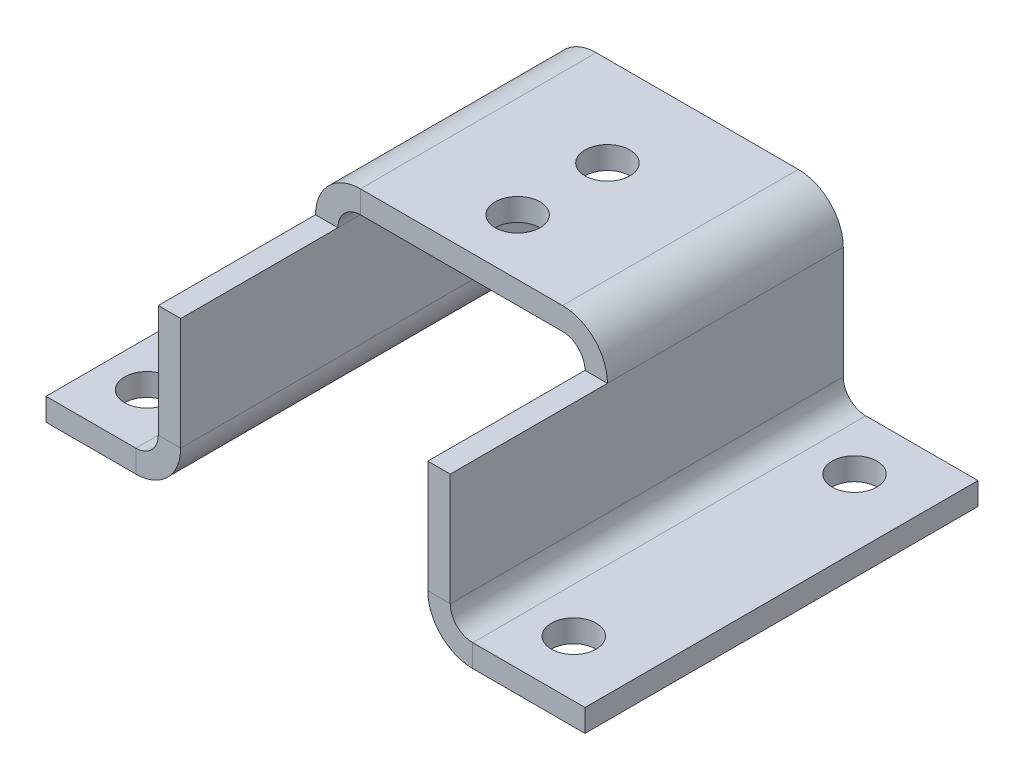
SolidWorks part; units mm, degrees
note: The reader was unsure of these and kept them because the rebuilt part matched: flange length of "Edge-Flange1", "Edge-Flange2", "Edge-Flange3", "Edge-Flange4".
ref_plane "Front Plane" through (0, 0, 0) normal (0, 0, 1) x (1, 0, 0)
ref_plane "Top Plane" through (0, 0, 0) normal (0, 1, 0) x (1, 0, 0)
ref_plane "Right Plane" through (0, 0, 0) normal (1, 0, 0) x (0, 0, -1)
sketch "Sketch1" plane through (0, 0, 0) normal (0, 1, 0) x (1, 0, 0)
  line L1 (6, -17.5) -> (-6, -17.5)
  line L2 (6, -17.5) -> (6, 17.5)
  line L3 (6, 17.5) -> (-6, 17.5)
  line L4 (-6, -17.5) -> (-6, 17.5)
  line L5 (6, -17.5) -> (-6, 17.5) construction
  line L6 (6, 17.5) -> (-6, -17.5) construction
  point P0 (0, 0)
  dimension "D1" = 12
  dimension "D2" = 35
base flange "Base-Flange1" sketch "Sketch1" thickness 2 reverse thickness direction no parameters "D1"=2
edge flange "Edge-Flange1" sketch "Sketch8" flange angle 90 flange length 16 flange position material inside bend radius 2 thickness 2 relief rectangular parameters "D6"=10
sketch "Sketch8" plane through (6, 0, 0) normal (1, 0, 0) x (0, 0, -1)
  line L0 (-17.5, 0) -> (17.5, 0) construction
  line L1 (-17.5, 0) -> (17.5, 0)
  line L2 (-17.5, 0) -> (-17.5, 16)
  line L3 (-17.5, 16) -> (17.5, 16)
  line L4 (17.5, 16) -> (17.5, 0)
bend "EdgeBend1" bend radius 2 bend angle 90 parameters "D5"=1
edge flange "Edge-Flange2" sketch "Sketch11" flange angle 90 flange length 24 flange position material inside bend radius 2 thickness 2 relief rectangular parameters "D6"=10
sketch "Sketch11" plane through (6, 16, 0) normal (0, 1, 0) x (0, 0, 1)
  line L0 (-17.5, 0) -> (17.5, 0) construction
  line L1 (-17.5, 0) -> (17.5, 0)
  line L2 (-17.5, 0) -> (-17.5, 24)
  line L3 (-17.5, 24) -> (17.5, 24)
  line L4 (17.5, 24) -> (17.5, 0)
bend "EdgeBend2" bend radius 2 bend angle 90 parameters "D5"=2
edge flange "Edge-Flange3" sketch "Sketch14" flange angle 90 flange length 16 flange position material inside bend radius 2 thickness 2 relief rectangular parameters "D6"=10
sketch "Sketch14" plane through (30, 14, 0) normal (1, 0, 0) x (0, 0, 1)
  line L0 (17.5, 0) -> (-17.5, 0) construction
  line L1 (17.5, 0) -> (-17.5, 0)
  line L2 (-17.5, 0) -> (-17.5, 16)
  line L3 (-17.5, 16) -> (17.5, 16)
  line L4 (17.5, 16) -> (17.5, 0)
bend "EdgeBend3" bend radius 2 bend angle 90 parameters "D5"=3
edge flange "Edge-Flange4" sketch "Sketch17" flange angle 90 flange length 12 flange position material inside bend radius 2 thickness 2 relief rectangular parameters "D6"=10
sketch "Sketch17" plane through (30, -2, 0) normal (0, -1, 0) x (0, 0, -1)
  line L0 (-17.5, 0) -> (17.5, 0) construction
  line L1 (-17.5, 0) -> (17.5, 0)
  line L2 (-17.5, 0) -> (-17.5, 12)
  line L3 (-17.5, 12) -> (17.5, 12)
  line L4 (17.5, 12) -> (17.5, 0)
bend "EdgeBend4" bend radius 2 bend angle 90 parameters "D5"=4
sketch "Sketch18" plane through (0, 16, 0) normal (0, 1, 0) x (1, 0, 0)
  line L0 (32, -17.5) -> (32, 17.5) construction
  line L1 (2, -17.5) -> (32, -17.5)
  line L2 (2, -17.5) -> (2, -3.5)
  line L3 (2, -3.5) -> (32, -3.5)
  line L4 (32, -17.5) -> (32, -3.5)
  dimension "D1" = 14
extrude "Cut-Extrude1" cut sketch "Sketch18" against normal blind 4 normal cut yes
sketch "Sketch19" plane through (0, 0, 0) normal (0, 1, 0) x (1, 0, 0)
  line L0 (2, 17.5) -> (-6, 17.5) construction
  circle A0 centre (-2, 12.5) radius 2
  circle A1 centre (-2, -12.5) radius 2
  circle A2 centre (36, 12.5) radius 2
  circle A3 centre (36, -12.5) radius 2
  point P14 (-2, 17.5)
  dimension "D1" = 4
  dimension "D2" = 38
  dimension "D4" = 25
  dimension "D3" = 5
extrude "Cut-Extrude2" cut sketch "Sketch19" against normal through all normal cut yes
sketch "Sketch20" plane through (0, 16, 0) normal (0, 1, 0) x (1, 0, 0)
  line L0 (26, 17.5) -> (8, 17.5) construction
  line L1 (26, -3.5) -> (8, -3.5) construction
  circle A0 centre (17, 9.5) radius 2
  circle A1 centre (17, 1.5) radius 2
  point P9 (17, -3.5)
  dimension "D1" = 16
  dimension "D2" = 8
  dimension "D3" = 4
  dimension "D4" = 4
extrude "Cut-Extrude4" cut sketch "Sketch20" against normal through all normal cut yes
sketch "Bend-Lines1" [suppressed] plane through (0, 0, 0) normal (0, 1, 0) x (1, 0, 0)
sketch "Bounding-Box1" [suppressed] plane through (0, 0, 0) normal (0, 1, 0) x (1, 0, 0)
sheet metal parameters "Sheet-Metal1" thickness 2 parameters "D1"=2
flat pattern "Flat-Pattern1" [suppressed]
sketch "Bend-Lines2" plane through (0, 0, 0) normal (0, 1, 0) x (1, 0, 0)
sketch3d "Bounding-Box2" [suppressed]
  line L0 (6, 17.5, 0) -> (6, -17.5, 0) construction
  line L1 (-6, 17.5, 0) -> (-6, -17.5, 0) construction
  line L2 (6, 17.5, 0) -> (-6, 17.5, 0) construction
  line L3 (6, -17.5, 0) -> (-6, -17.5, 0) construction
sheet metal parameters "Sheet-Metal2" thickness 2 parameters "D1"=2
flat pattern "Flat-Pattern1" [suppressed]
sketch "Bend-Lines2" plane through (0, 0, 0) normal (0, 1, 0) x (1, 0, 0)
  line L0 (4.3562, -17.5) -> (4.3562, 17.5) construction
  line L1 (4.3562, -17.5) -> (4.3562, 17.5) construction
sketch3d "Bounding-Box2" [suppressed]
  line L0 (-6, 17.5, 0) -> (-6, -17.5, 0) construction
  line L1 (19.7124, 17.5, 0) -> (19.7124, -17.5, 0) construction
  line L2 (-6, 17.5, 0) -> (19.7124, 17.5, 0) construction
  line L3 (-6, -17.5, 0) -> (19.7124, -17.5, 0) construction
bend of the flat pattern "Flatten-<EdgeBend1>1"
sheet metal parameters "Sheet-Metal3" thickness 2 parameters "D1"=2
flat pattern "Flat-Pattern1" [suppressed]
sketch "Bend-Lines2" plane through (0, 0, 0) normal (0, 1, 0) x (1, 0, 0)
  line L0 (4.3562, -17.5) -> (4.3562, 17.5) construction
  line L1 (4.3562, -17.5) -> (4.3562, 17.5) construction
  line L2 (18.0686, -17.5) -> (18.0686, 17.5) construction
  line L3 (18.0686, -17.5) -> (18.0686, 17.5) construction
sketch3d "Bounding-Box2" [suppressed]
  line L0 (42.4248, -17.5, 0) -> (-6, -17.5, 0) construction
  line L1 (42.4248, 17.5, 0) -> (-6, 17.5, 0) construction
  line L2 (42.4248, -17.5, 0) -> (42.4248, 17.5, 0) construction
  line L3 (-6, -17.5, 0) -> (-6, 17.5, 0) construction
bend of the flat pattern "Flatten-<EdgeBend2>1"
bend of the flat pattern "Flatten-<EdgeBend1>1"
sheet metal parameters "Sheet-Metal4" thickness 2 parameters "D1"=2
flat pattern "Flat-Pattern1" [suppressed]
sketch "Bend-Lines2" plane through (0, 0, 0) normal (0, 1, 0) x (1, 0, 0)
  line L0 (4.3562, -17.5) -> (4.3562, 17.5) construction
  line L1 (4.3562, -17.5) -> (4.3562, 17.5) construction
  line L2 (18.0686, -17.5) -> (18.0686, 17.5) construction
  line L3 (18.0686, -17.5) -> (18.0686, 17.5) construction
  line L4 (40.781, -17.5) -> (40.781, 17.5) construction
  line L5 (40.781, -17.5) -> (40.781, 17.5) construction
sketch3d "Bounding-Box2" [suppressed]
  line L0 (57.1372, -17.5, 0) -> (-6, -17.5, 0) construction
  line L1 (57.1372, 17.5, 0) -> (-6, 17.5, 0) construction
  line L2 (57.1372, -17.5, 0) -> (57.1372, 17.5, 0) construction
  line L3 (-6, -17.5, 0) -> (-6, 17.5, 0) construction
bend of the flat pattern "Flatten-<EdgeBend2>1"
bend of the flat pattern "Flatten-<EdgeBend3>1"
bend of the flat pattern "Flatten-<EdgeBend1>1"
sheet metal parameters "Sheet-Metal5" thickness 2 parameters "D1"=2
flat pattern "Flat-Pattern1" [suppressed]
sketch "Bend-Lines2" plane through (0, 0, 0) normal (0, 1, 0) x (1, 0, 0)
  line L0 (4.3562, -17.5) -> (4.3562, 17.5) construction
  line L1 (4.3562, -17.5) -> (4.3562, 17.5) construction
  line L2 (19.0686, -17.5) -> (19.0686, 17.5) construction
  line L3 (19.0686, -17.5) -> (19.0686, 17.5) construction
  line L4 (41.781, -17.5) -> (41.781, 17.5) construction
  line L5 (41.781, -17.5) -> (41.781, 17.5) construction
  line L6 (56.4934, -17.5) -> (56.4934, 17.5) construction
  line L7 (56.4934, -17.5) -> (56.4934, 17.5) construction
sketch3d "Bounding-Box2" [suppressed]
  line L0 (68.8496, -17.5, 0) -> (-6, -17.5, 0) construction
  line L1 (68.8496, 17.5, 0) -> (-6, 17.5, 0) construction
  line L2 (68.8496, -17.5, 0) -> (68.8496, 17.5, 0) construction
  line L3 (-6, -17.5, 0) -> (-6, 17.5, 0) construction
bend of the flat pattern "Flatten-<EdgeBend2>1"
bend of the flat pattern "Flatten-<EdgeBend3>1"
bend of the flat pattern "Flatten-<EdgeBend4>1"
bend of the flat pattern "Flatten-<EdgeBend1>1"
sheet metal parameters "Sheet-Metal6" thickness 2 parameters "D1"=2
flat pattern "Flat-Pattern1" [suppressed]
sketch "Bend-Lines2" plane through (0, 0, 0) normal (0, 1, 0) x (1, 0, 0)
  line L0 (4.3562, -17.5) -> (4.3562, 17.5) construction
  line L1 (4.3562, -17.5) -> (4.3562, 17.5) construction
  line L2 (19.0686, -3.5) -> (19.0686, 17.5) construction
  line L3 (19.0686, -3.5) -> (19.0686, 17.5) construction
  line L4 (41.781, -3.5) -> (41.781, 17.5) construction
  line L5 (41.781, -3.5) -> (41.781, 17.5) construction
  line L6 (56.4934, -17.5) -> (56.4934, 17.5) construction
  line L7 (56.4934, -17.5) -> (56.4934, 17.5) construction
sketch3d "Bounding-Box2" [suppressed]
  line L0 (68.8496, -17.5, 0) -> (-6, -17.5, 0) construction
  line L1 (68.8496, 17.5, 0) -> (-6, 17.5, 0) construction
  line L2 (68.8496, -17.5, 0) -> (68.8496, 17.5, 0) construction
  line L3 (-6, -17.5, 0) -> (-6, 17.5, 0) construction
bend of the flat pattern "Flatten-<EdgeBend4>1"
bend of the flat pattern "Flatten-<EdgeBend3>1"
bend of the flat pattern "Flatten-<EdgeBend2>1"
bend of the flat pattern "Flatten-<EdgeBend1>1"
sheet metal parameters "Sheet-Metal7" thickness 2 parameters "D1"=2
flat pattern "Flat-Pattern1" [suppressed]
sketch "Bend-Lines2" plane through (0, 0, 0) normal (0, 1, 0) x (1, 0, 0)
  line L8 (4.3562, -17.5) -> (4.3562, 17.5) construction
  line L9 (4.3562, -17.5) -> (4.3562, 17.5) construction
  point P2 (19.0686, -3.5)
  point P3 (19.0686, 17.5)
  point P4 (41.781, -3.5)
  point P5 (41.781, 17.5)
  point P6 (56.4934, -17.5)
  point P7 (56.4934, 17.5)
sketch3d "Bounding-Box2" [suppressed]
  line L0 (-6, 17.5, 0) -> (-6, -17.5, 0) construction
  line L1 (20.7124, 17.5, 0) -> (20.7124, -17.5, 0) construction
  line L2 (-6, 17.5, 0) -> (20.7124, 17.5, 0) construction
  line L3 (-6, -17.5, 0) -> (20.7124, -17.5, 0) construction
bend of the flat pattern "Flatten-<EdgeBend4>1"
bend of the flat pattern "Flatten-<EdgeBend3>1"
bend of the flat pattern "Flatten-<EdgeBend2>1"
bend of the flat pattern "Flatten-<EdgeBend1>1"
sheet metal parameters "Sheet-Metal9" thickness 2 parameters "D1"=2
flat pattern "Flat-Pattern1" [suppressed]
sketch "Bend-Lines2" plane through (0, 0, 0) normal (0, 1, 0) x (1, 0, 0)
  line L0 (4.3562, -17.5) -> (4.3562, 17.5) construction
  line L1 (4.3562, -17.5) -> (4.3562, 17.5) construction
  line L2 (19.0686, -3.5) -> (19.0686, 17.5) construction
  line L3 (19.0686, -3.5) -> (19.0686, 17.5) construction
  line L4 (41.781, -3.5) -> (41.781, 17.5) construction
  line L5 (41.781, -3.5) -> (41.781, 17.5) construction
  line L6 (56.4934, -17.5) -> (56.4934, 17.5) construction
  line L7 (56.4934, -17.5) -> (56.4934, 17.5) construction
sketch3d "Bounding-Box2" [suppressed]
  line L0 (68.8496, -17.5, 0) -> (-6, -17.5, 0) construction
  line L1 (68.8496, 17.5, 0) -> (-6, 17.5, 0) construction
  line L2 (68.8496, -17.5, 0) -> (68.8496, 17.5, 0) construction
  line L3 (-6, -17.5, 0) -> (-6, 17.5, 0) construction
bend of the flat pattern "Flatten-<EdgeBend2>1"
bend of the flat pattern "Flatten-<EdgeBend3>1"
bend of the flat pattern "Flatten-<EdgeBend4>1"
bend of the flat pattern "Flatten-<EdgeBend1>1"
sketch "Sketch20-1" [suppressed] plane through (13.4248, 0, 0) normal (0, 1, 0) x (1, 0, 0)
  line L0 (55.4248, 17.5) -> (-19.4248, 17.5) construction
  circle A0 centre (17, 9.5) radius 2
  circle A1 centre (17, 1.5) radius 2
  dimension "D1" = 16
  dimension "D2" = 8
  dimension "D3" = 4
  dimension "D4" = 4
